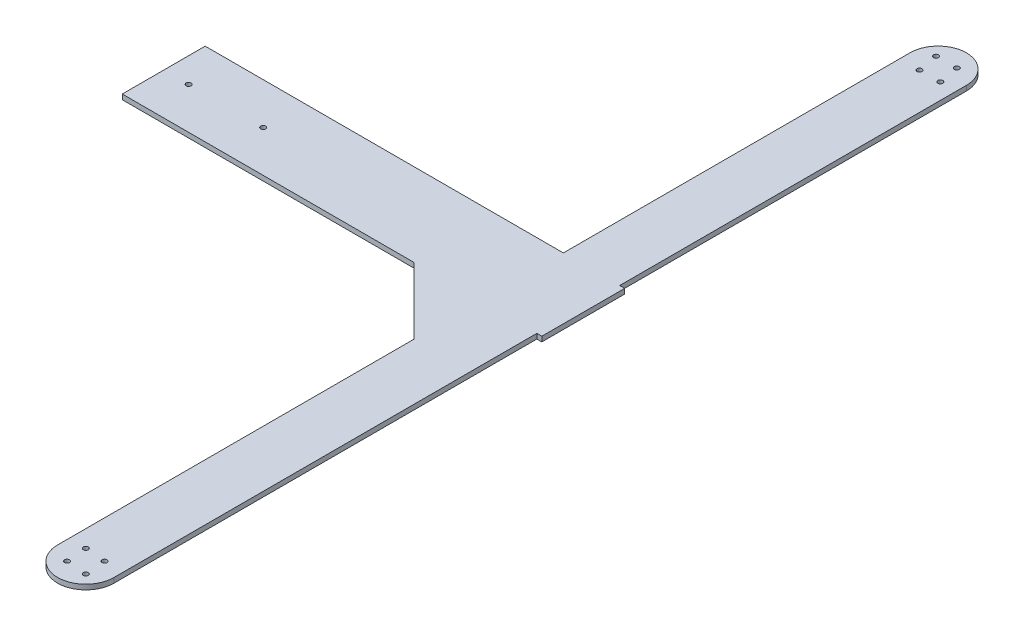
SolidWorks part; units mm, degrees
ref_plane "Front Plane" through (0, 0, 0) normal (0, 0, 1) x (1, 0, 0)
ref_plane "Top Plane" through (0, 0, 0) normal (0, 1, 0) x (1, 0, 0)
ref_plane "Right Plane" through (0, 0, 0) normal (1, 0, 0) x (0, 0, -1)
sketch "Sketch1" plane through (0, 0, 0) normal (0, 1, 0) x (1, 0, 0)
  line L0 (0, 0) -> (176, 0)
  line L1 (216, -40) -> (216, -255)
  line L2 (0, 0) -> (0, 50)
  line L3 (0, 50) -> (216, 50)
  line L4 (216, 50) -> (216, 259.0603)
  line L5 (250, -255) -> (250, 259.0603)
  line L6 (50, -120) -> (250, -120) construction
  line L7 (50, 150) -> (50, -120) construction
  line L8 (50, 150) -> (250, 120) construction
  line L9 (176, 0) -> (216, -40)
  line L10 (227.9078, 252.8902) -> (238.0922, 265.2304) construction
  line L11 (240.327, 253.0134) -> (225.673, 265.1073) construction
  line L12 (227.3431, -260.6569) -> (238.6569, -249.3431) construction
  line L13 (0, 25) -> (250, 25) construction
  line L14 (226.2825, -248.2825) -> (239.7175, -261.7175) construction
  arc A0 (216, -255) -> (250, -255) centre (233, -255) ccw
  arc A1 (216, 259.0603) -> (250, 259.0603) centre (233, 259.0603) cw
  circle A2 centre (233, -255) radius 135 construction
  circle A3 centre (233, 259.0603) radius 135 construction
  circle A4 centre (238.0922, 265.2304) radius 1.5
  circle A5 centre (225.673, 265.1073) radius 1.5
  circle A6 centre (227.9078, 252.8902) radius 1.5
  circle A7 centre (240.327, 253.0134) radius 1.5
  circle A8 centre (226.2825, -248.2825) radius 1.5
  circle A9 centre (238.6569, -249.3431) radius 1.5
  circle A10 centre (239.7175, -261.7175) radius 1.5
  circle A11 centre (227.3431, -260.6569) radius 1.5
  circle A12 centre (15, 25) radius 1.5
  circle A13 centre (50, 25) radius 1.5
  point P1 (216, 0)
  point P12 (250, 120)
  point P13 (250, -120)
  point P14 (50, 150)
  point P15 (50, -120)
  dimension "D1" = 17
  dimension "D3" = 270
  dimension "D4" = 270
  dimension "D12" = 3
  dimension "D13" = 3
  dimension "D14" = 3
  dimension "D15" = 3
  dimension "D20" = 3
  dimension "D21" = 3
  dimension "D22" = 3
  dimension "D23" = 3
  dimension "D24" = 3
  dimension "D25" = 3
  dimension "D27" = 50
  dimension "D2" = 50
  dimension "D5" = 240
  dimension "D6" = 200
  dimension "D7" = 50
  dimension "D8" = 120
  dimension "D9" = 16
  dimension "D10" = 19
  dimension "D16" = 270
  dimension "D17" = 45
  dimension "D18" = 16
  dimension "D19" = 19
  dimension "D26" = 15
extrude "Boss-Extrude1" add sketch "Sketch1" along normal blind 3 contours L1 A0 L5 L8 L4 L3 L7 L0 L9 A11 A10 A9 A8 | L7 L3 L2 L0 | A1 L4 L8 L5 A7 A6 A5 A4 region at (187.1561, 0, -9.901)
sketch "Эскиз3" plane through (250, 0, 0) normal (1, 0, 0) x (0, 0, -1)
  line L0 (0, 3) -> (0, 0)
  line L1 (0, 0) -> (50, 0)
  line L2 (50, 0) -> (50, 3)
  line L3 (50, 3) -> (0, 3)
extrude "Бобышка-Вытянуть1" add sketch "Эскиз3" along normal blind 3
sketch "Эскиз4" plane through (0, 3, 0) normal (0, 1, 0) x (1, 0, 0)
  circle A0 centre (60, 25) radius 1.5
extrude "Вырез-Вытянуть1" cut sketch "Эскиз4" against normal blind 10
sketch "Эскиз5" plane through (0, 3, 0) normal (0, 1, 0) x (1, 0, 0)
  circle A0 centre (50, 25) radius 1.5
extrude "Бобышка-Вытянуть2" add sketch "Эскиз5" against normal blind 3
